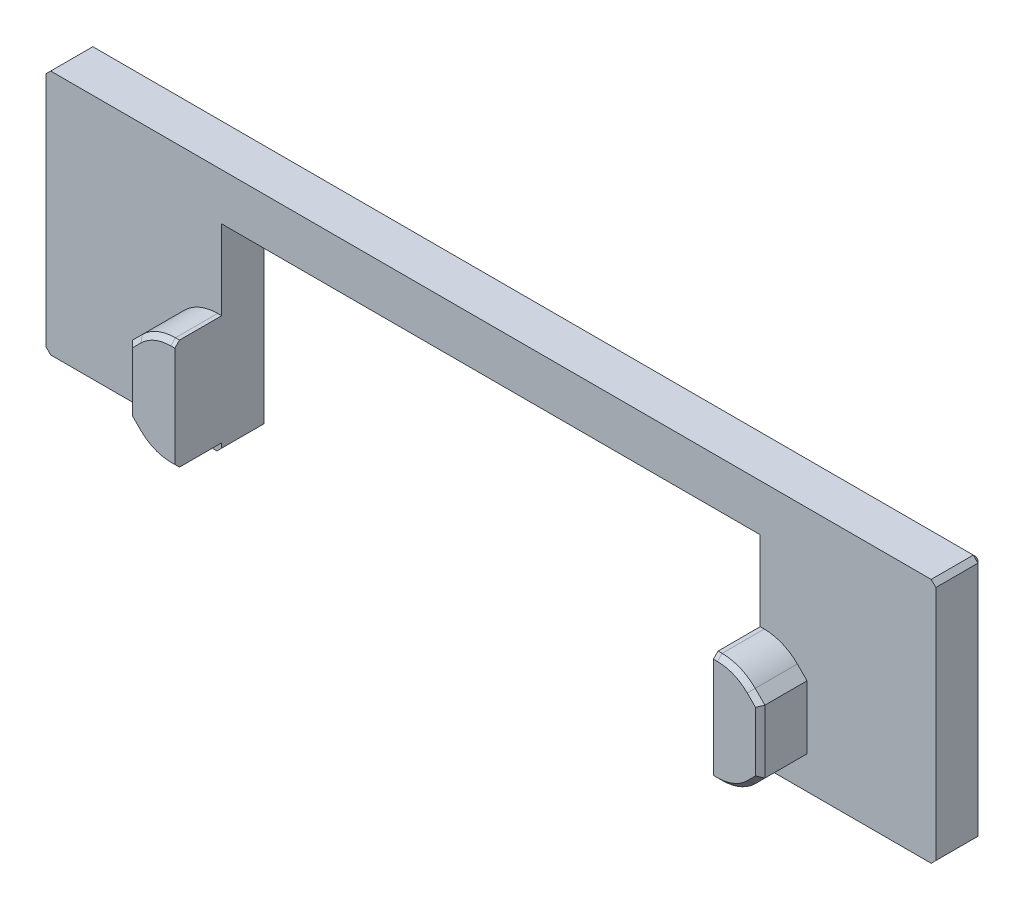
SolidWorks part; units mm, degrees
ref_plane "Front" through (0, 0, 0) normal (0, 0, 1) x (1, 0, 0)
ref_plane "Top" through (0, 0, 0) normal (0, 1, 0) x (1, 0, 0)
ref_plane "Right" through (0, 0, 0) normal (1, 0, 0) x (0, 0, -1)
sketch "Sketch1" plane through (0, 0, 0) normal (0, 0, 1) x (1, 0, 0)
  line L0 (-18.8, 5.25) -> (18.8, 5.25)
  line L5 (19, 5.05) -> (19, -5.05)
  line L6 (18.8, -5.25) -> (11.7, -5.25)
  line L7 (11.5, -5.05) -> (11.5, 3.25)
  line L8 (11.5, 3.25) -> (-11.5, 3.25)
  line L9 (-11.5, 3.25) -> (-11.5, -5.05)
  line L10 (-11.7, -5.25) -> (-18.8, -5.25)
  line L11 (-19, -5.05) -> (-19, 5.05)
  line L12 (19, 5.05) -> (19, -5.05) construction
  line L13 (18.8, -5.25) -> (11.5, -5.25) construction
  line L14 (18.8, 5.25) -> (-18.8, 5.25) construction
  line L15 (19, -5.05) -> (18.8, -5.25)
  line L16 (-11.5, -5.25) -> (-18.8, -5.25) construction
  line L17 (-19, 5.05) -> (-19, -5.05) construction
  line L18 (11.7, -5.25) -> (11.5, -5.05)
  line L19 (18.8, 5.25) -> (19, 5.05)
  line L20 (-19, 5.05) -> (-18.8, 5.25)
  line L21 (-18.8, -5.25) -> (-19, -5.05)
  line L22 (-11.5, -5.05) -> (-11.7, -5.25)
  point P0 (-19, 5.25)
  point P1 (19, 5.25)
  point P2 (19, -5.25)
  point P4 (11.5, -5.25)
  point P6 (-19, -5.25)
  point P13 (-11.5, -5.25)
extrude "Boss-Extrude1" add sketch "Sketch1" against normal blind 2
sketch "Sketch3" plane through (0, 0, 0) normal (0, 0, 1) x (1, 0, 0)
  line L3 (11.5, -5.05) -> (11.5, 3.25) construction
  line L4 (11.5, -4.85) -> (11.5, -0.15)
  line L20 (13.5, -3.85) -> (13.5, -1.15)
  line L21 (13.5, -3.85) -> (13.5, -1.15)
  line L22 (13.5, -1.15) -> (13.0858, -0.7358)
  line L23 (13.5, -1.15) -> (13.0858, -0.7358)
  line L24 (11.6716, -0.15) -> (10.8284, -0.15)
  line L25 (11.6716, -0.15) -> (11.5, -0.15)
  line L26 (9.4142, -0.7358) -> (9, -1.15)
  line L28 (9, -1.15) -> (9, -3.85)
  line L30 (9, -3.85) -> (9.4142, -4.2642)
  line L32 (10.8284, -4.85) -> (11.6716, -4.85)
  line L33 (11.5, -4.85) -> (11.6716, -4.85)
  line L34 (13.0858, -4.2642) -> (13.5, -3.85)
  line L35 (13.0858, -4.2642) -> (13.5, -3.85)
  arc A18 (13.0858, -0.7358) -> (11.6716, -0.15) centre (11.6716, -2.15) ccw
  arc A19 (13.0858, -0.7358) -> (11.6716, -0.15) centre (11.6716, -2.15) ccw
  arc A20 (10.8284, -0.15) -> (9.4142, -0.7358) centre (10.8284, -2.15) ccw
  arc A22 (9.4142, -4.2642) -> (10.8284, -4.85) centre (10.8284, -2.85) ccw
  arc A24 (11.6716, -4.85) -> (13.0858, -4.2642) centre (11.6716, -2.85) ccw
  arc A25 (11.6716, -4.85) -> (13.0858, -4.2642) centre (11.6716, -2.85) ccw
  line M20 (11.5, 3.25) -> (11.5, -5.05)
  dimension "D1" = 0
extrude "Boss-Extrude3" add sketch "Sketch3" along normal blind 2 contours L4 | L33 A25 L35 L21 L23 A19 L25 M20 region at (12.42, -2.5, 0)
mirror "Mirror3" about plane through (0, 0, 0) normal (1, 0, 0) of "Boss-Extrude3"
chamfer "Deburs" distance 0.2 angle 45 28 edges at (11.5, -0.9, -2) (11.6, -5.15, -2) (15.25, -5.25, -2) (18.9, -5.15, -2) (19, 0, -2) (18.9, 5.15, -2) (0, 5.25, -2) (-18.9, 5.15, -2) (-19, 0, -2) (-18.9, -5.15, -2) (-15.25, -5.25, -2) (-11.6, -5.15, -2) (-11.5, -0.9, -2) (0, 3.25, -2) (-11.5858, -4.85, 2) (-13.2929, -4.0571, 2) (-12.4369, -4.6978, 2) (-13.5, -2.5, 2) (-13.2929, -0.9429, 2) (-11.5858, -0.15, 2) (-12.4369, -0.3022, 2) (11.5858, -4.85, 2) (13.2929, -4.0571, 2) (12.4369, -4.6978, 2) (13.5, -2.5, 2) (13.2929, -0.9429, 2) (11.5858, -0.15, 2) (12.4369, -0.3022, 2)
